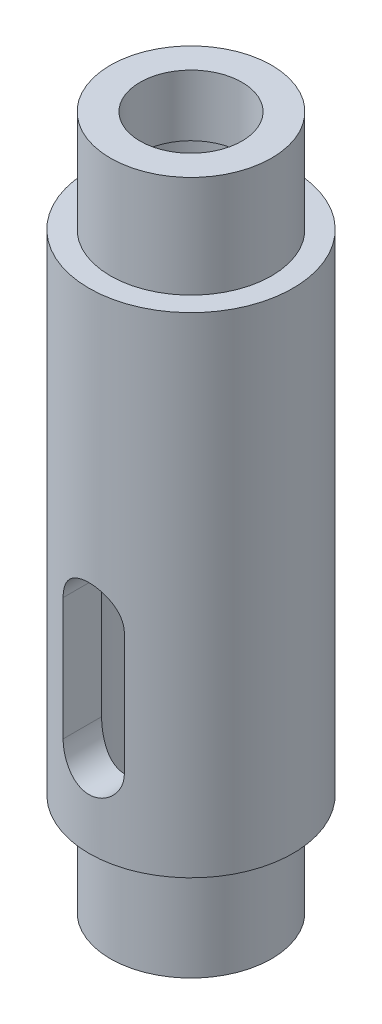
SolidWorks part; units mm, degrees
ref_plane "Przednia" through (0, 0, 0) normal (0, 0, 1) x (1, 0, 0)
ref_plane "Górna" through (0, 0, 0) normal (0, 1, 0) x (1, 0, 0)
ref_plane "Prawa" through (0, 0, 0) normal (1, 0, 0) x (0, 0, -1)
sketch "Szkic1" plane through (0, 0, 0) normal (0, 1, 0) x (1, 0, 0)
  circle A0 centre (0, 0) radius 5
  dimension "D1" = 10
extrude "Dodanie-wyciągnięcie1" add sketch "Szkic1" along normal blind 34
sketch "Szkic4" plane through (0, 0, 0) normal (0, 0, 1) x (1, 0, 0)
  line L0 (0, 15) -> (0, 9) construction
  line L1 (1.5, 15) -> (1.5, 9)
  line L2 (-1.5, 15) -> (-1.5, 9)
  line L4 (5, 34) -> (-5, 34) construction
  arc A0 (1.5, 15) -> (-1.5, 15) centre (0, 15) ccw
  arc A1 (-1.5, 9) -> (1.5, 9) centre (0, 9) ccw
  point P2 (0, 12)
  dimension "D1" = 3
  dimension "D2" = 6
  dimension "D3" = 22
extrude "Wytnij-wyciągnięcie1" cut sketch "Szkic4" against normal mid plane 60
sketch "Szkic5" plane through (0, 0, 0) normal (0, -1, 0) x (1, 0, 0)
  circle A0 centre (0, 0) radius 3.25
  dimension "D1" = 6.5
extrude "Wytnij-wyciągnięcie2" cut sketch "Szkic5" against normal offset from surface (31 mm away) 3 up to face at (0, 34, 5)
sketch "Szkic6" plane through (0, 34, 0) normal (0, 1, 0) x (1, 0, 0)
  circle A0 centre (0, 0) radius 2.5
  dimension "D1" = 5
extrude "Wytnij-wyciągnięcie3" cut sketch "Szkic6" against normal through all
sketch "Szkic7" plane through (0, 0, 0) normal (0, 0, 1) x (1, 0, 0)
  line L0 (-5, 17) -> (5, 17) construction
  line L1 (-5, 34) -> (-5, 0) construction
  line L2 (5, 0) -> (5, 34) construction
  line L3 (-3.95, 32.8) -> (-3.8, 32.8)
  line L4 (-3.8, 32.8) -> (-3.8, 32)
  line L5 (-3.8, 32) -> (-3.95, 32)
  line L6 (-3.95, 32.8) -> (-3.95, 34)
  line L7 (-3.95, 1.2) -> (-3.95, 2) construction
  line L8 (-3.95, 5) -> (-3.95, 2)
  line L9 (-5, 5) -> (-3.95, 5)
  line L10 (-3.95, 1.2) -> (-3.95, 0)
  line L12 (-5, 29) -> (-3.95, 29)
  line L13 (-3.95, 29) -> (-3.95, 32)
  line L14 (-3.95, 32.8) -> (-3.95, 32) construction
  line L15 (5, 34) -> (-5, 34) construction
  line L16 (-3.8, 2) -> (-3.95, 2)
  line L17 (-3.8, 1.2) -> (-3.8, 2)
  line L18 (-3.95, 1.2) -> (-3.8, 1.2)
  line L19 (0, 34) -> (0, 0) construction
  line L20 (-3.95, 34) -> (-5, 34)
  line L21 (-5, 34) -> (-5, 29)
  line L22 (-5, 5) -> (-5, 0)
  line L23 (-5, 0) -> (-3.95, 0)
  dimension "D1" = 5
  dimension "D2" = 1.05
  dimension "D3" = 3
  dimension "D4" = 3.8
  dimension "D5" = 0.8
revolve "Wycięcie-obrót2" cut sketch "Szkic7" angle 360 about axis through (0, 34, 0) along (0, -1, 0)
sketch "Szkic8" plane through (0, 32, 0) normal (0, 1, 0) x (1, 0, 0)
  circle A0 centre (0, 0) radius 3.95
  circle A1 centre (0, 0) radius 3.8
extrude "Dodanie-wyciągnięcie2" add sketch "Szkic8" along normal blind 2
sketch "Szkic9" plane through (0, 2, 0) normal (0, -1, 0) x (1, 0, 0)
  circle A0 centre (0, 0) radius 3.95
  circle A1 centre (0, 0) radius 3.8
extrude "Dodanie-wyciągnięcie3" add sketch "Szkic9" along normal blind 2
